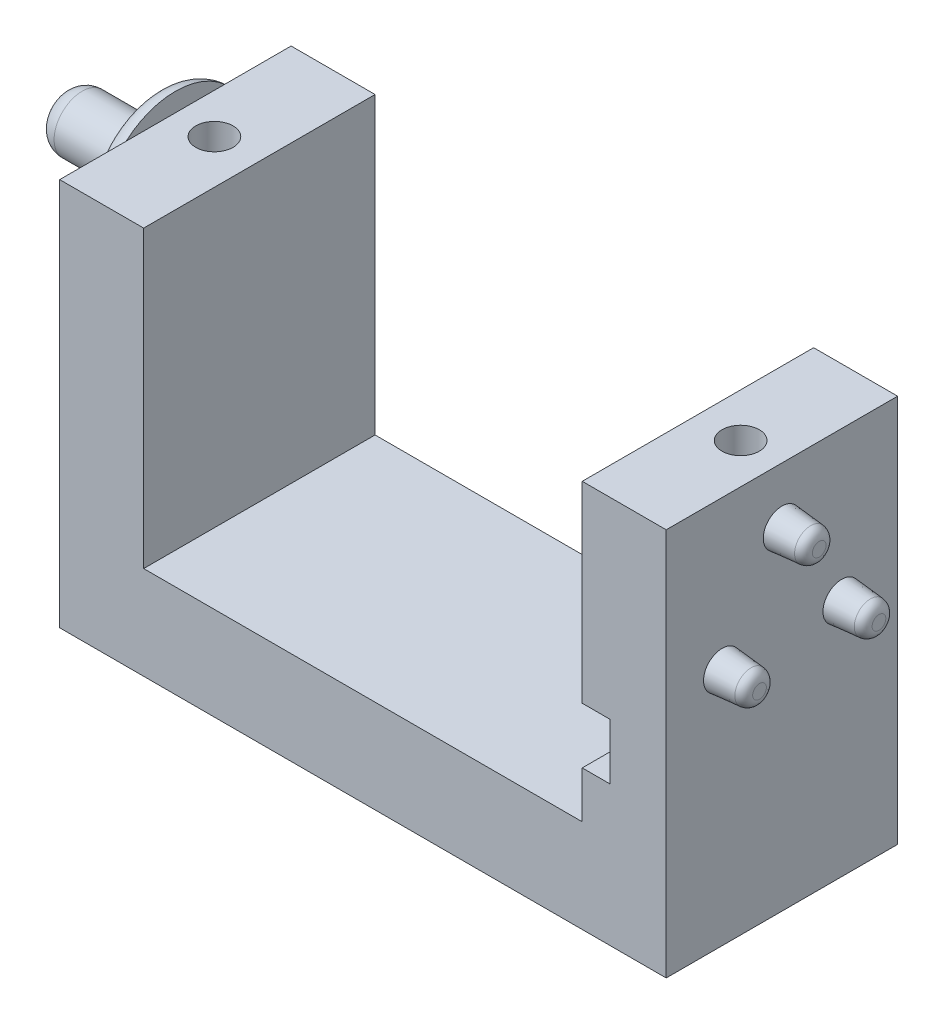
SolidWorks part; units mm, degrees
ref_plane "Front Plane" through (0, 0, 0) normal (0, 0, 1) x (1, 0, 0)
ref_plane "Top Plane" through (0, 0, 0) normal (0, 1, 0) x (1, 0, 0)
ref_plane "Right Plane" through (0, 0, 0) normal (1, 0, 0) x (0, 0, -1)
sketch "Sketch1" plane through (0, 0, 0) normal (0, 1, 0) x (1, 0, 0)
  line L1 (-16.25, 6.2) -> (16.25, 6.2)
  line L2 (-16.25, 6.2) -> (-16.25, -6.2)
  line L3 (-16.25, -6.2) -> (16.25, -6.2)
  line L4 (16.25, 6.2) -> (16.25, -6.2)
  line L5 (-16.25, 6.2) -> (16.25, -6.2) construction
  line L6 (-16.25, -6.2) -> (16.25, 6.2) construction
  point P0 (0, 0)
  dimension "D1" = 32.5
  dimension "D2" = 12.4
extrude "Boss-Extrude1" add sketch "Sketch1" along normal blind 5
sketch "Sketch3" plane through (0, 5, 0) normal (0, 1, 0) x (1, 0, 0)
  line L0 (-16.25, -6.2) -> (16.25, -6.2) construction
  line L1 (-16.25, 6.2) -> (-11.75, 6.2)
  line L2 (-16.25, 6.2) -> (-16.25, -6.2)
  line L3 (-16.25, -6.2) -> (-11.75, -6.2)
  line L4 (-11.75, 6.2) -> (-11.75, -6.2)
  line L6 (16.25, 6.2) -> (11.75, 6.2)
  line L7 (16.25, 6.2) -> (16.25, -6.2)
  line L8 (16.25, -6.2) -> (11.75, -6.2)
  line L9 (11.75, 6.2) -> (11.75, -6.2)
  dimension "D1" = 4.5
  dimension "D2" = 4.5
extrude "Boss-Extrude2" add sketch "Sketch3" along normal blind 15.8
sketch "Sketch4" plane through (0, 20.8, 0) normal (0, 1, 0) x (1, 0, 0)
  line L0 (-16.25, 6.2) -> (-16.25, -6.2) construction
  line L1 (-16.25, -6.2) -> (-11.75, -6.2) construction
  line L2 (16.25, -6.2) -> (16.25, 6.2) construction
  line L3 (11.75, -6.2) -> (16.25, -6.2) construction
  circle A0 centre (14.1, -0.06) radius 1
  circle A1 centre (-14.1, -0.06) radius 1
  dimension "D3" = 2
  dimension "D6" = 2
  dimension "D1" = 2.15
  dimension "D2" = 6.14
  dimension "D4" = 2.15
  dimension "D5" = 6.14
extrude "Cut-Extrude1" cut sketch "Sketch4" against normal blind 5
sketch "Sketch5" plane through (16.25, 0, 0) normal (1, 0, 0) x (0, 0, -1)
  line L0 (-6.2, 20.8) -> (6.2, 20.8) construction
  line L1 (-6.2, 20.8) -> (-6.2, 0) construction
  line L2 (6.2, 20.8) -> (6.2, 0) construction
  circle A0 centre (0, 17.8) radius 1
  circle A1 centre (3.2, 12.8) radius 1
  circle A2 centre (-3.2, 12.8) radius 1
  circle A3 centre (0, 14.276) radius 3.524 construction
  dimension "D4" = 2
  dimension "D5" = 2
  dimension "D6" = 2
  dimension "D10" = 7.048
  dimension "D1" = 3
  dimension "D2" = 5
  dimension "D3" = 5
  dimension "D7" = 3
  dimension "D8" = 3
  dimension "D9" = 6.2
extrude "Boss-Extrude3" add sketch "Sketch5" along normal blind 2 draft 5
sketch "Sketch6" plane through (-16.25, 0, 0) normal (-1, 0, 0) x (0, 0, 1)
  line L1 (6.2, 20.8) -> (6.2, 0) construction
  line L2 (-6.2, 20.8) -> (6.2, 20.8) construction
  circle A0 centre (0, 17.8) radius 4
  dimension "D4" = 8
  dimension "D1" = 6.2
  dimension "D2" = 3
  dimension "D3" = 17.8
extrude "Boss-Extrude4" add sketch "Sketch6" along normal blind 1
sketch "Sketch7" plane through (-17.25, 0, 0) normal (-1, 0, 0) x (0, 0, 1)
  circle A0 centre (0, 17.8) radius 1.5
  dimension "D1" = 3
extrude "Boss-Extrude5" add sketch "Sketch7" along normal blind 5
fillet "Fillet1" radius 1 1 edges at (-22.25, 17.8, 1.5)
fillet "Fillet2" radius 1 1 edges at (-17.25, 17.8, 4)
fillet "Fillet3" radius 0.5 3 edges at (18.25, 12.8, -4.025) (18.25, 12.8, 2.375) (18.25, 17.8, -0.825)
sketch "Sketch10" plane through (0, 0, -6.2) normal (0, 0, -1) x (-1, 0, 0)
  line L0 (-11.75, 20.8) -> (-11.75, 5) construction
  line L1 (-11.75, 10.5) -> (-13.25, 10.5)
  line L2 (-11.75, 10.5) -> (-11.75, 7.5)
  line L3 (-11.75, 7.5) -> (-13.25, 7.5)
  line L4 (-13.25, 10.5) -> (-13.25, 7.5)
  line L5 (-16.25, 0) -> (16.25, 0) construction
  dimension "D1" = 10.5
  dimension "D2" = 3
  dimension "D3" = 1.5
extrude "Cut-Extrude4" cut sketch "Sketch10" against normal through all
